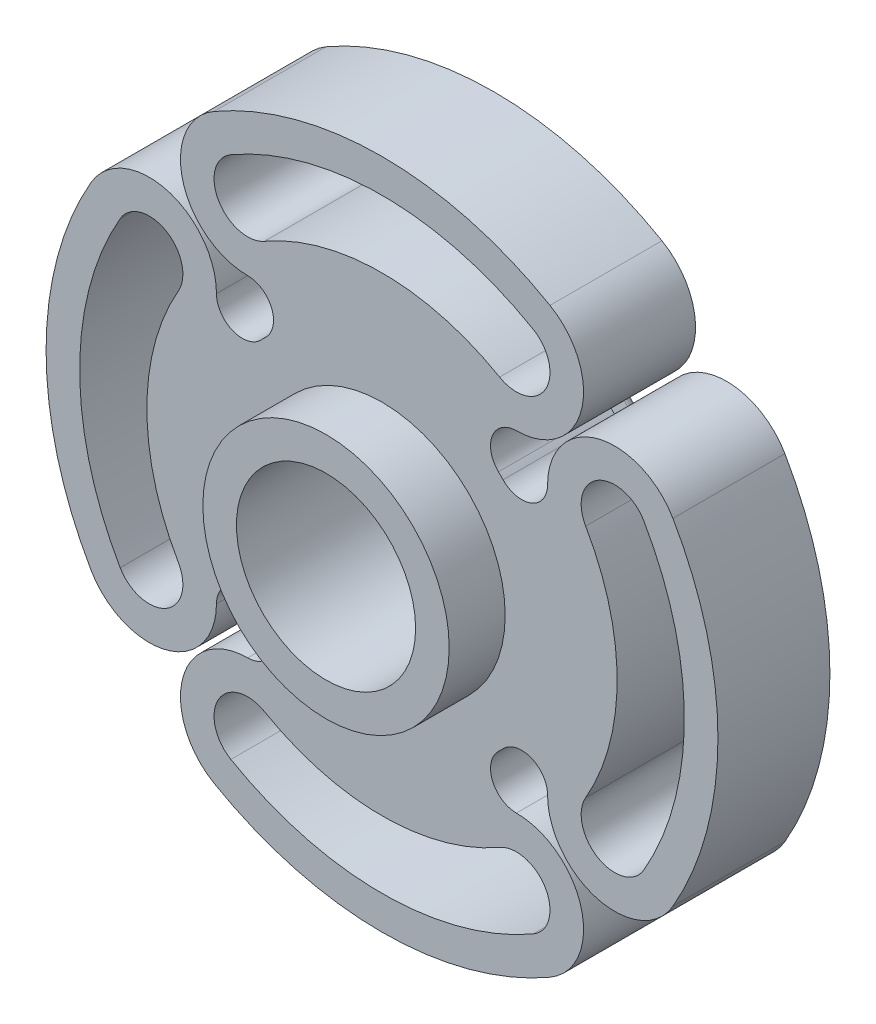
SolidWorks part; units mm, degrees
ref_plane "Front Plane" through (0, 0, 0) normal (0, 0, 1) x (1, 0, 0)
ref_plane "Top Plane" through (0, 0, 0) normal (0, 1, 0) x (1, 0, 0)
ref_plane "Right Plane" through (0, 0, 0) normal (1, 0, 0) x (0, 0, -1)
sketch "Sketch1" plane through (0, 0, 0) normal (0, 0, 1) x (1, 0, 0)
  line L0 (0, 0) -> (13272.0433, 0) construction
  line L1 (0, 0) -> (0, 13272.0433) construction
  arc A0 (-10.3988, 10.8104) -> (-10.8104, 10.3988) centre (0, 0) ccw
  arc A1 (12, 20.7846) -> (-12, 20.7846) centre (0, 0) ccw construction
  arc A2 (13.5, 23.3827) -> (-13.5, 23.3827) centre (0, 0) ccw
  arc A3 (10.5, 18.1865) -> (-10.5, 18.1865) centre (0, 0) ccw
  arc A4 (10.5, 18.1865) -> (13.5, 23.3827) centre (12, 20.7846) ccw
  arc A5 (-13.5, 23.3827) -> (-10.5, 18.1865) centre (-12, 20.7846) ccw
  arc A6 (12, 20.7846) -> (-12, 20.7846) centre (0, 0) ccw construction
  arc A7 (15, 25.9808) -> (-15, 25.9808) centre (0, 0) ccw
  arc A9 (12, 14.7846) -> (15, 25.9808) centre (12, 20.7846) ccw
  arc A10 (-15, 25.9808) -> (-12, 14.7846) centre (-12, 20.7846) ccw
  arc A11 (-12, 14.7846) -> (-10.3988, 10.8104) centre (-12, 12.4749) cw
  arc A12 (12, 14.7846) -> (10.3988, 10.8104) centre (12, 12.4749) ccw
  arc A13 (25.9808, -15) -> (25.9808, 15) centre (0, 0) ccw
  arc A14 (14.7846, -12) -> (25.9808, -15) centre (20.7846, -12) ccw
  arc A15 (25.9808, 15) -> (14.7846, 12) centre (20.7846, 12) ccw
  arc A16 (14.7846, 12) -> (10.8104, 10.3988) centre (12.4749, 12) cw
  arc A17 (14.7846, -12) -> (10.8104, -10.3988) centre (12.4749, -12) ccw
  arc A18 (20.7846, -12) -> (20.7846, 12) centre (0, 0) ccw construction
  arc A19 (20.7846, -12) -> (20.7846, 12) centre (0, 0) ccw construction
  arc A20 (23.3827, -13.5) -> (23.3827, 13.5) centre (0, 0) ccw
  arc A21 (18.1865, -10.5) -> (18.1865, 10.5) centre (0, 0) ccw
  arc A22 (18.1865, -10.5) -> (23.3827, -13.5) centre (20.7846, -12) ccw
  arc A23 (23.3827, 13.5) -> (18.1865, 10.5) centre (20.7846, 12) ccw
  arc A24 (-15, -25.9808) -> (15, -25.9808) centre (0, 0) ccw
  arc A25 (-12, -14.7846) -> (-15, -25.9808) centre (-12, -20.7846) ccw
  arc A26 (15, -25.9808) -> (12, -14.7846) centre (12, -20.7846) ccw
  arc A27 (12, -14.7846) -> (10.3988, -10.8104) centre (12, -12.4749) cw
  arc A28 (-12, -14.7846) -> (-10.3988, -10.8104) centre (-12, -12.4749) ccw
  arc A29 (-12, -20.7846) -> (12, -20.7846) centre (0, 0) ccw construction
  arc A30 (-12, -20.7846) -> (12, -20.7846) centre (0, 0) ccw construction
  arc A31 (-13.5, -23.3827) -> (13.5, -23.3827) centre (0, 0) ccw
  arc A32 (-10.5, -18.1865) -> (10.5, -18.1865) centre (0, 0) ccw
  arc A33 (-10.5, -18.1865) -> (-13.5, -23.3827) centre (-12, -20.7846) ccw
  arc A34 (13.5, -23.3827) -> (10.5, -18.1865) centre (12, -20.7846) ccw
  arc A35 (-25.9808, 15) -> (-25.9808, -15) centre (0, 0) ccw
  arc A36 (-14.7846, 12) -> (-25.9808, 15) centre (-20.7846, 12) ccw
  arc A37 (-25.9808, -15) -> (-14.7846, -12) centre (-20.7846, -12) ccw
  arc A38 (-14.7846, -12) -> (-10.8104, -10.3988) centre (-12.4749, -12) cw
  arc A39 (-14.7846, 12) -> (-10.8104, 10.3988) centre (-12.4749, 12) ccw
  arc A40 (-20.7846, 12) -> (-20.7846, -12) centre (0, 0) ccw construction
  arc A41 (-20.7846, 12) -> (-20.7846, -12) centre (0, 0) ccw construction
  arc A42 (-23.3827, 13.5) -> (-23.3827, -13.5) centre (0, 0) ccw
  arc A43 (-18.1865, 10.5) -> (-18.1865, -10.5) centre (0, 0) ccw
  arc A44 (-18.1865, 10.5) -> (-23.3827, 13.5) centre (-20.7846, 12) ccw
  arc A45 (-23.3827, -13.5) -> (-18.1865, -10.5) centre (-20.7846, -12) ccw
  arc A46 (-10.8104, -10.3988) -> (-10.3988, -10.8104) centre (0, 0) ccw
  arc A47 (10.3988, -10.8104) -> (10.8104, -10.3988) centre (0, 0) ccw
  arc A48 (10.8104, 10.3988) -> (10.3988, 10.8104) centre (0, 0) ccw
  circle A49 centre (0, 0) radius 8
  circle A50 centre (0, 0) radius 11
  point P9 (0, 24)
  point P14 (0, 24)
  point P25 (24, 0)
  point P35 (24, 0)
  point P48 (0, -24)
  point P53 (0, -24)
  point P66 (-24, 0)
  point P71 (-24, 0)
  point P82 (0, 0)
  dimension "D1" = 30
  dimension "D2" = 3
  dimension "D3" = 6
  dimension "D4" = 24
  dimension "D6" = 4
  dimension "D7" = 22
  dimension "D8" = 16
  dimension "D5" = 60
extrude "Boss-Extrude1" add sketch "Sketch1" along normal mid plane 20 contours A49 | A50 region at (0, 0, 0)
extrude "Boss-Extrude3" add sketch "Sketch1<5>" along normal mid plane 10 contours A16 A48 A12 A9 A7 A10 A11 A0 A39 A36 A35 A37 A38 A46 A28 A25 A24 A26 A27 A47 A17 A14 A13 A15 A50 A5 A2 A4 A3 A23 A20 A22 A21 A34 A31 A33 A32 A45 A42 A44 A43 region at (-9.0706, 13.6552, 0)
sketch "Sketch1<5>" plane through (0, 0, 0) normal (0, 0, 1) x (1, 0, 0) same geometry as "Sketch1"
fillet "Fillet2" radius 1 2 edges at (8, 0, -10) (11, 0, -10)
fillet "Fillet3" radius 1 1 edges at (11, 0, -5)
